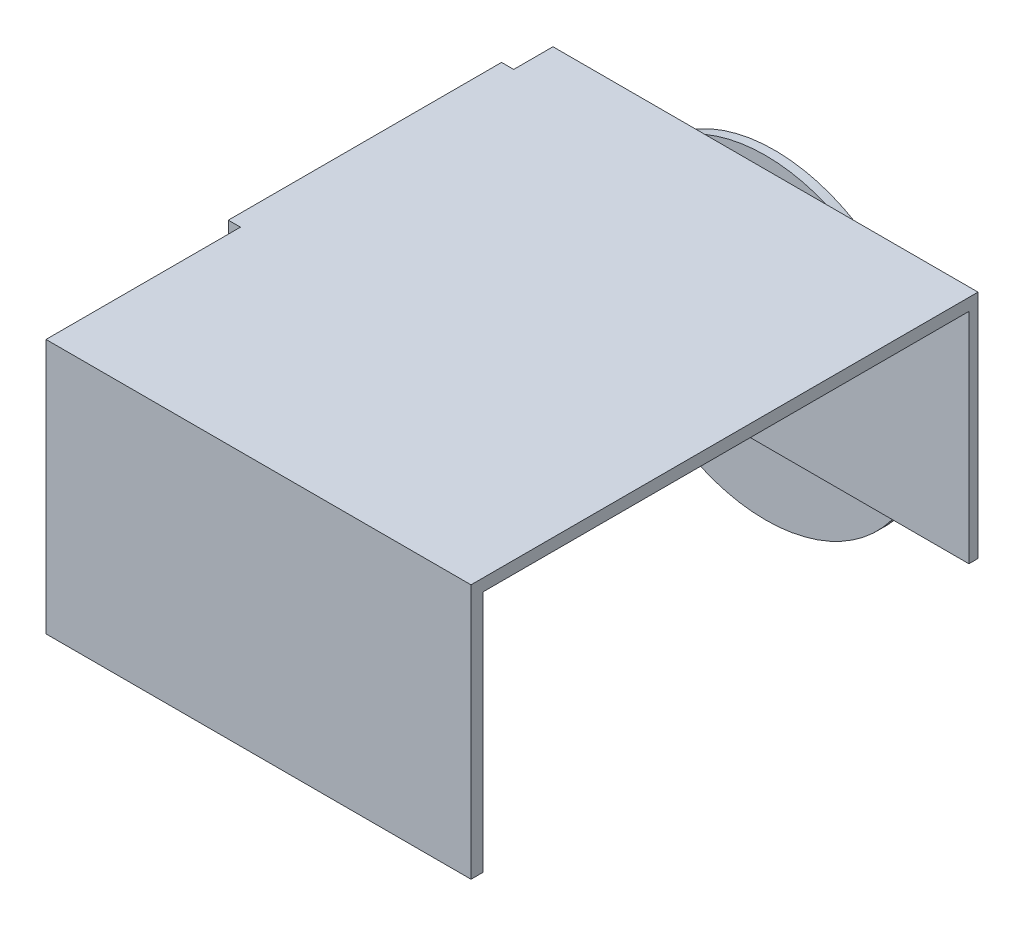
SolidWorks part; units mm, degrees
ref_plane "前视基准面" through (0, 0, 0) normal (0, 0, 1) x (1, 0, 0)
ref_plane "上视基准面" through (0, 0, 0) normal (0, 1, 0) x (1, 0, 0)
ref_plane "右视基准面" through (0, 0, 0) normal (1, 0, 0) x (0, 0, -1)
sketch "草图1" plane through (0, 0, 0) normal (0, 0, 1) x (1, 0, 0)
  circle A0 centre (0, 0) radius 26
extrude "凸台-拉伸1" add sketch "草图1" along normal blind 1.5
sketch "草图2" plane through (0, 0, 1.5) normal (0, 0, 1) x (1, 0, 0)
  line L1 (-35, 24) -> (-35, -14)
  line L2 (-35, -14) -> (-21.9089, -14)
  line L3 (0, 26) -> (0, -9.3207) construction
  line L4 (35, -14) -> (21.9089, -14)
  line L5 (35, 24) -> (35, -14)
  line L6 (21.9089, -14) -> (-21.9089, -14)
  line L7 (0, 26) -> (0, 24) construction
  line L8 (0, 24) -> (-42.6939, 24) construction
  line L9 (-35, 24) -> (35, 24)
  circle A0 centre (0, 0) radius 26 construction
extrude "凸台-拉伸2" add sketch "草图2" along normal blind 1.5
sketch "草图3" plane through (0, 0, 3) normal (0, 0, 1) x (1, 0, 0)
  line L0 (-35, 24) -> (-35, 22)
  line L1 (-35, 24) -> (-35, -14) construction
  line L2 (-35, 22) -> (35, 22)
  line L3 (35, -14) -> (35, 24) construction
  line L4 (35, 22) -> (35, 24)
  line L5 (35, 24) -> (-35, 24)
extrude "凸台-拉伸3" add sketch "草图3" along normal blind 82
sketch "草图4" plane through (0, 22, 0) normal (0, -1, 0) x (1, 0, 0)
  line L0 (-35, 85) -> (-35, 83)
  line L1 (-35, 85) -> (-35, 3) construction
  line L2 (-35, 83) -> (35, 83)
  line L3 (35, 85) -> (35, 3) construction
  line L4 (35, 83) -> (35, 85)
  line L5 (-35, 85) -> (35, 85) construction
  line L6 (35, 85) -> (-35, 85)
extrude "凸台-拉伸4" add sketch "草图4" along normal blind 40
sketch "草图5" plane through (-35, 0, 0) normal (-1, 0, 0) x (0, 0, 1)
  line L3 (7.9707, -18) -> (77.9707, -18)
  line L6 (30.4707, 22) -> (52.9707, 22) construction
  line L7 (77.9707, -11) -> (77.9707, -18) construction
  line L8 (77.9707, -11) -> (77.9707, -18)
  line L9 (30.4707, 22) -> (7.9707, 22) construction
  line L10 (7.9707, 22) -> (7.9707, -18)
  line L11 (7.9707, 2) -> (52.9707, 2) construction
  line L12 (77.9707, -11) -> (52.9707, -11) construction
  line L13 (52.9707, -11) -> (52.9707, 22) construction
  line L14 (52.9707, 22) -> (52.9707, -11)
  line L15 (52.9707, -11) -> (77.9707, -11)
  line L16 (7.9707, 22) -> (7.9707, 24)
  line L17 (85, 24) -> (1.5, 24) construction
  line L18 (7.9707, 24) -> (52.9707, 24)
  line L19 (52.9707, 24) -> (52.9707, 22)
  circle A0 centre (30.4707, 2) radius 18.5
extrude "凸台-拉伸5" add sketch "草图5" along normal blind 2
